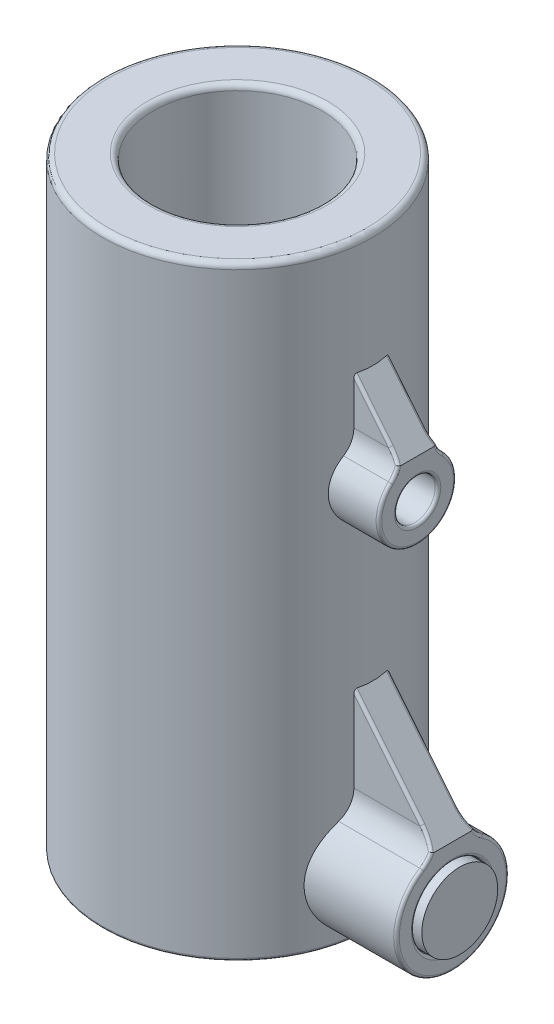
SolidWorks part; units mm, degrees
ref_plane "Front Plane" through (0, 0, 0) normal (0, 0, 1) x (1, 0, 0)
ref_plane "Top Plane" through (0, 0, 0) normal (0, 1, 0) x (1, 0, 0)
ref_plane "Right Plane" through (0, 0, 0) normal (1, 0, 0) x (0, 0, -1)
sketch "Sketch1" plane through (0, 0, 0) normal (0, 1, 0) x (1, 0, 0)
  circle A0 centre (0, 0) radius 7.6
  circle A1 centre (0, 0) radius 9.6
  dimension "D1" = 15.2
  dimension "D2" = 2
extrude "Boss-Extrude1" add sketch "Sketch1" along normal blind 20
sketch "Sketch2" plane through (0, 20, 0) normal (0, 1, 0) x (1, 0, 0)
  circle A0 centre (0, 0) radius 6
  circle A1 centre (0, 0) radius 9.6 construction
  circle A2 centre (0, 0) radius 9.6
  dimension "D1" = 12
extrude "Boss-Extrude2" add sketch "Sketch2" along normal blind 20
fillet "Fillet1" radius 0.4 2 edges at (0, 40, 6) (0, 40, 9.6)
sketch "Sketch3" plane through (0, 20, 0) normal (0, -1, 0) x (1, 0, 0)
  circle A1 centre (0, 0) radius 6 construction
  circle A2 centre (0, 0) radius 5.7
  circle A3 centre (0, 0) radius 5.7
  circle A4 centre (0, 0) radius 6
  dimension "D1" = 0.3
extrude "Boss-Extrude3" add sketch "Sketch3" against normal blind 1
sketch "Sketch5" plane through (0, 0, 0) normal (0, -1, 0) x (1, 0, 0)
  circle A0 centre (0, 0) radius 7.6 construction
  circle A1 centre (0, 0) radius 9.6
  circle A2 centre (0, 0) radius 9.6
  circle A3 centre (0, 0) radius 7.6
  dimension "D1" = 0
extrude "Boss-Extrude4" add sketch "Sketch5" along normal blind 3
sketch "Sketch4" plane through (0, 0, 0) normal (1, 0, 0) x (0, 0, -1)
  line L0 (0, 1.25) -> (0, 0) construction
  line L1 (0, 0) -> (0, 1.25) construction
  line L2 (0, 1.25) -> (0, 25) construction
  line L3 (5.7, 21) -> (-5.7, 21) construction
  line L4 (0, 2.7) -> (-2.6105, 2.7) construction
  line L5 (-2.6105, 2.7) -> (-2.6105, 20) construction
  line L6 (-5.7, 20) -> (5.7, 20) construction
  circle A0 centre (0, 1.25) radius 1.45
  circle A1 centre (0, 25) radius 1.45
  dimension "D1" = 2.9
  dimension "D3" = 2.9
  dimension "D2" = 17.3
  dimension "D4" = 4
extrude "Cut-Extrude1" cut sketch "Sketch4" against normal blind 24 and the other way blind 29
fillet "Fillet4" radius 0.2 2 edges at (0, 20, -5.7) (0, 21, -5.7)
ref_plane "Plane1" through (12.8, 0, 0) normal (1, 0, 0) x (0, 0, -1)
sketch "Sketch6" plane through (12.8, 0, 0) normal (1, 0, 0) x (0, 0, -1)
  circle A0 centre (0, 1.25) radius 1.45 construction
  circle A1 centre (0, 1.25) radius 1.45
  circle A2 centre (0, 1.25) radius 4
  dimension "D1" = 8
extrude "Boss-Extrude5" add sketch "Sketch6" against normal up to surface (3.3101 mm away) up to face at (0, 39.6, 9.6)
sketch "Sketch7" plane through (12.8, 0, 0) normal (1, 0, 0) x (0, 0, -1)
  circle A0 centre (0, 1.25) radius 2.7
  dimension "D1" = 5.4
extrude "Boss-Extrude6" add sketch "Sketch7" along normal blind 3 separate body
sketch "Sketch8" plane through (12.8, 0, 0) normal (-1, 0, 0) x (0, 0, 1)
  circle A0 centre (0, 1.25) radius 1.5
  dimension "D1" = 3
extrude "Boss-Extrude7" add sketch "Sketch8" along normal blind 6
sketch "Sketch9" plane through (12.8, 0, 0) normal (1, 0, 0) x (0, 0, -1)
  circle A0 centre (0, 1.25) radius 2.75
  circle A1 centre (0, 1.25) radius 4
  circle A2 centre (0, 1.25) radius 4
  dimension "D2" = 5.5
  dimension "D1" = 0
extrude "Boss-Extrude8" add sketch "Sketch9" along normal blind 2.5
sketch "Sketch10" plane through (12.8, 0, 0) normal (1, 0, 0) x (0, 0, -1)
  circle A0 centre (0, 25) radius 1.45
  circle A1 centre (0, 25) radius 2.75
  dimension "D1" = 5.5
extrude "Boss-Extrude9" add sketch "Sketch10" against normal up to surface (3.3101 mm away) up to face at (8.7451, 0.6869, 3.9602)
sketch "Sketch11" plane through (0, 0, 0) normal (0, 0, 1) x (1, 0, 0)
  line L0 (12.8, 27.75) -> (8.0225, 33.6497)
  line L1 (8.0225, 33.6497) -> (8.0225, 26.45)
  line L2 (8.0225, 26.45) -> (12.8, 26.45)
  line L3 (12.8, 22.25) -> (12.8, 27.75) construction
  line L4 (12.8, 26.45) -> (12.8, 27.75)
  line L5 (12.8, 26.45) -> (6, 26.45) construction
  line L6 (15.3, 5.25) -> (8.0225, 14.237)
  line L7 (15.3, -2.75) -> (15.3, 5.25) construction
  line L8 (8.0225, 14.237) -> (8.0225, 4)
  line L9 (8.0225, 4) -> (15.3, 4)
  line L10 (15.3, 4) -> (12.8, 4) construction
  line L11 (15.3, 4) -> (15.3, 5.25)
  point P17 (0, 0)
  point P18 (15.3, 5.25)
  dimension "D1" = 39
  dimension "D2" = 39
extrude "Boss-Extrude10" add sketch "Sketch11" along normal mid plane 2.5
fillet "Fillet5" radius 2 4 edges at (11.1591, 27.4495, -1.25) (12.4091, 5.0497, -1.25) (11.1591, 27.4495, 1.25) (12.4091, 5.0497, 1.25)
fillet "Fillet6" radius 0.2 25 edges at (12.5158, 28.101, -1.2832) (12.5158, 28.101, 1.2832) (14.8939, 5.7515, -1.3249) (14.8939, 5.7515, 1.3249) (12.8, 27.3494, -1.5894) (12.8, 22.25, 0) (15.3, 4.896, -1.8193) (15.3, -2.75, 0) (12.8, 25, -1.45) (-5.8292, 24.7129, -1.4213) (5.8292, 25.2871, -1.4213) (12.8, 1.25, -1.45) (-7.4666, 0.9457, -1.4177) (7.4666, 1.5543, -1.4177) (-9.4951, 24.685, -1.4154) (-9.4951, 0.935, -1.4154) (0, -3, -7.6) (0, -3, -9.6) (10.87, 30.1333, -1.25) (10.87, 30.1333, 1.25) (11.9866, 9.3417, -1.25) (11.9866, 9.3417, 1.25) (15.3, 1.25, -2.75) (12.8, 27.3494, 1.5894) (15.3, 4.896, 1.8193)
